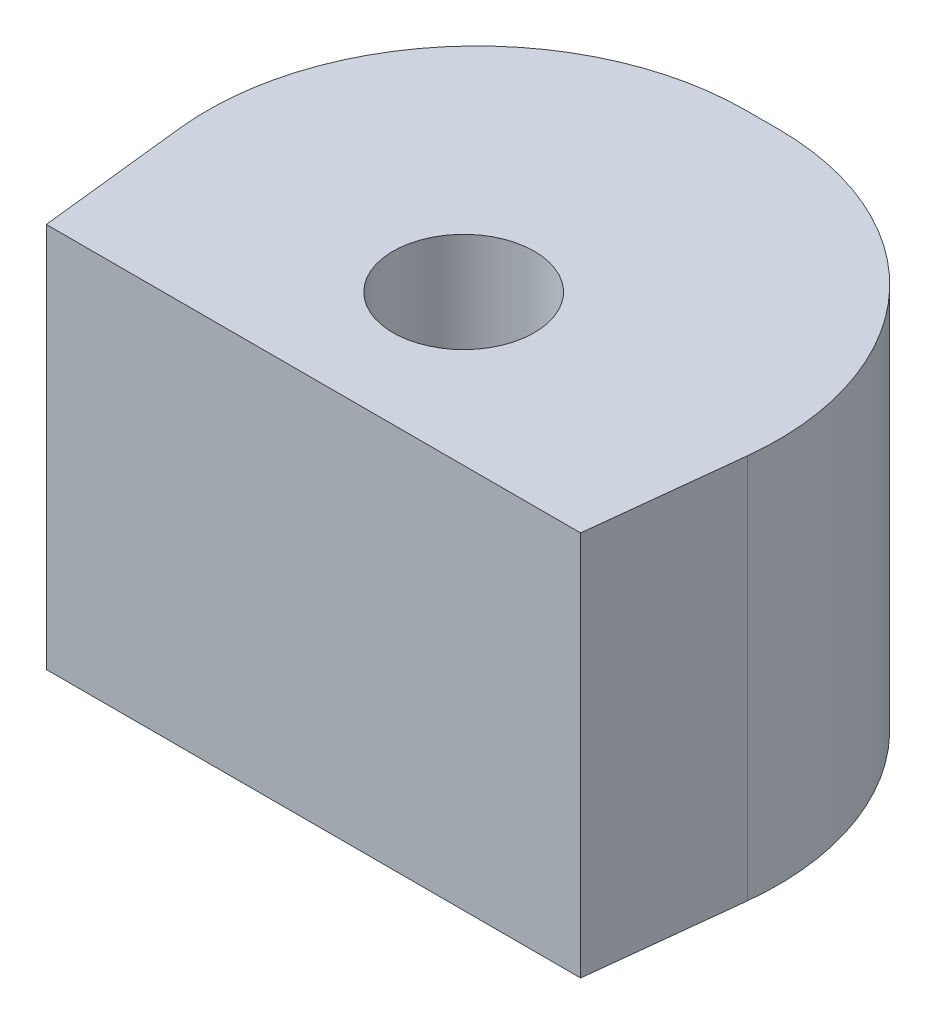
SolidWorks part; units mm, degrees
ref_plane "Front Plane" through (0, 0, 0) normal (0, 0, 1) x (1, 0, 0)
ref_plane "Top Plane" through (0, 0, 0) normal (0, 1, 0) x (1, 0, 0)
ref_plane "Right Plane" through (0, 0, 0) normal (1, 0, 0) x (0, 0, -1)
sketch "Sketch1" plane through (0, 0, 0) normal (0, 1, 0) x (1, 0, 0)
  line L0 (1.1081, 1.7265) -> (-45.0799, 1.7265) construction
  line L1 (-45.0799, 1.7265) -> (-45.0799, -11.2275) construction
  line L2 (-45.0799, -11.2275) -> (43.7517, -11.2275) construction
  line L3 (1.1081, 103.3269) -> (1.1081, -99.8738) construction
  line L4 (-45.0799, -11.2275) -> (-45.0799, -20.7525) construction
  line L5 (-28.2049, 1.7265) -> (-28.2049, -3.6075) construction
  line L6 (-9.9553, -3.6075) -> (-6.7697, -3.6075)
  line L7 (-28.2049, -3.6075) -> (-9.9553, -3.6075) construction
  line L8 (-6.7697, -3.6075) -> (1.1081, -3.6075) construction
  line L9 (8.9859, -3.6075) -> (12.1715, -3.6075)
  line L10 (12.1715, -3.6075) -> (18.1346, -3.6075) construction
  line L11 (12.1715, -3.6075) -> (18.1346, -3.6075) construction
  line L12 (18.1346, -3.6075) -> (29.3788, -3.6075) construction
  line L13 (1.1081, -3.6075) -> (8.9859, -3.6075) construction
  line L14 (-6.7697, -3.6075) -> (8.9859, -3.6075)
  circle A0 centre (1.1081, -11.3265) radius 1.9844 construction
  circle A1 centre (1.1081, -11.3265) radius 1.9844
  spline S0 degree 3 poles (1.1081, -99.8738) (4.5273, -73.5318) (7.9866, -47.1872) (10.6029, -20.7525) knots 0 0 0 0 0.38497 0.38497 0.38497 0.38497
  spline S3 degree 3 poles (1.1081, -99.8738) (-2.3112, -73.5318) (-5.7704, -47.1872) (-8.3867, -20.7525) knots 0 0 0 0 0.38497 0.38497 0.38497 0.38497
  spline S4 degree 3 poles (10.6029, -20.7525) (11.1, -15.7302) (11.6306, -10.016) (12.114, -4.2968) (12.1715, -3.6075) knots 0.38497 0.38497 0.38497 0.38497 0.458109 0.468132 0.468132 0.468132 0.468132
  spline S5 degree 3 poles (-8.3867, -20.7525) (-8.8838, -15.7302) (-9.4144, -10.016) (-9.8978, -4.2968) (-9.9553, -3.6075) knots 0.38497 0.38497 0.38497 0.38497 0.458109 0.468132 0.468132 0.468132 0.468132
  spline S8 degree 3 poles (12.1715, -3.6075) (12.8364, 4.367) (14.1908, 23.6726) (14.0058, 48.0803) (13.0188, 67.5796) (11.3266, 78.9472) (9.5869, 86.9693) (8.1237, 93.6397) (6.4505, 97.563) (4.8164, 101.3994) (2.3437, 102.5279) (1.1081, 103.3269) knots 0.468132 0.468132 0.468132 0.468132 0.584075 0.748482 0.821537 0.866809 0.914778 0.94069 0.965303 0.976863 1 1 1 1 construction
  spline S9 degree 3 poles (1.1081, 99.6196) (1.2739, 99.518) (1.6209, 99.2976) (2.0134, 99.0137) (2.3095, 98.7539) (2.4667, 98.5788) (2.6076, 98.3713) (2.8163, 97.9774) (3.0534, 97.4394) (3.4327, 96.5453) (3.8774, 95.496) (4.541, 93.8448) (5.2023, 91.9048) (5.8236, 89.3366) (6.4213, 86.5662) (7.0145, 83.8293) (7.767, 80.1951) (8.6007, 75.6781) (9.6391, 68.4081) (10.3034, 59.2354) (10.6788, 47.9926) (10.8555, 36.7918) (10.7415, 25.5951) (10.3009, 14.4244) (9.6564, 4.6878) (9.1767, -1.3266) (8.9859, -3.6075) knots 0.118744 0.118744 0.118744 0.118744 0.122149 0.125554 0.12896 0.132365 0.13577 0.139175 0.142581 0.145986 0.152796 0.159607 0.173228 0.186849 0.20047 0.214091 0.227711 0.254953 0.282195 0.336679 0.391163 0.445646 0.50013 0.554614 0.609098 0.642376 0.642376 0.642376 0.642376 construction
  spline S10 degree 3 poles (-7.1984, 1.7265) (-7.237, 2.2289) (-7.5577, 6.4638) (-8.0847, 14.4244) (-8.5253, 25.5951) (-8.6393, 36.7918) (-8.4626, 47.9926) (-8.0872, 59.2354) (-7.4229, 68.4081) (-6.3845, 75.6781) (-5.5508, 80.1951) (-4.7983, 83.8293) (-4.2051, 86.5662) (-3.6074, 89.3366) (-2.9861, 91.9048) (-2.3248, 93.8448) (-1.6612, 95.496) (-1.2165, 96.5453) (-0.8372, 97.4394) (-0.6001, 97.9774) (-0.3914, 98.3713) (-0.2505, 98.5788) (-0.0933, 98.7539) (0.2028, 99.0137) (0.5953, 99.2976) (0.9423, 99.518) (1.1081, 99.6196) knots 0.492798 0.492798 0.492798 0.492798 0.50013 0.554614 0.609098 0.663581 0.718065 0.772549 0.827033 0.854275 0.881516 0.895137 0.908758 0.922379 0.936 0.949621 0.956432 0.963242 0.966647 0.970053 0.973458 0.976863 0.980268 0.983674 0.987079 0.990484 0.990484 0.990484 0.990484 construction
  spline S11 degree 3 poles (-10.3826, 1.7265) (-10.8572, 7.9268) (-11.9611, 25.4575) (-11.7896, 48.0803) (-10.8026, 67.5796) (-9.1104, 78.9472) (-7.3707, 86.9693) (-5.9075, 93.6397) (-4.2343, 97.563) (-2.6002, 101.3994) (-0.1276, 102.5279) (1.1081, 103.3269) knots 0.493976 0.493976 0.493976 0.493976 0.584075 0.748482 0.821537 0.866809 0.914778 0.94069 0.965303 0.976863 1 1 1 1 construction
  spline S12 degree 3 poles (-9.9553, -3.6075) (-10.1035, -1.8299) (-10.2465, -0.0519) (-10.3826, 1.7265) knots 0.468132 0.468132 0.468132 0.468132 0.493976 0.493976 0.493976 0.493976 construction
  spline S13 degree 3 poles (-6.7697, -3.6075) (-6.9185, -1.8292) (-7.0618, -0.0511) (-7.1984, 1.7265) knots 0.466852 0.466852 0.466852 0.466852 0.492798 0.492798 0.492798 0.492798 construction
  dimension "D4" = 3.9688
  dimension "D1" = 12.954
  dimension "D2" = 9.525
  dimension "D3" = 5.334
extrude "Boss-Extrude1" add sketch "Sketch1" along normal blind 169.8727
sketch "Sketch2" plane through (0, 169.8727, 0) normal (0, 1, 0) x (1, 0, 0)
  line L1 (-9.9553, -3.6075) -> (25.8085, -3.6075)
  line L2 (-9.9553, -3.6075) -> (-9.9553, -26.3125)
  line L3 (-9.9553, -26.3125) -> (25.8085, -26.3125)
  line L4 (25.8085, -3.6075) -> (25.8085, -26.3125)
  circle A0 centre (1.1081, -11.3265) radius 1.9844 construction
  dimension "D1" = 14.986
extrude "Cut-Extrude1" cut sketch "Sketch2" against normal blind 23.0581
extrude "Cut-Extrude2" cut sketch "Sketch2<2>" along normal blind 23.0581 from surface starting at face at (-1.1046, 0, 29.7187)
sketch "Sketch2<2>" plane through (0, 169.8727, 0) normal (0, 1, 0) x (1, 0, 0) same geometry as "Sketch2"
fillet "Fillet1" radius 7.62 6 edges at (-7.8242, 11.5291, 26.3125) (10.0403, 11.5291, 26.3125) (12.1715, 84.9363, 3.6075) (-7.8242, 158.3436, 26.3125) (10.0403, 158.3436, 26.3125)
sketch "Sketch6" plane through (0, 0, 0) normal (0, -1, 0) x (1, 0, 0)
  line L0 (1.1081, 3.6075) -> (1.1081, 99.8738) construction
  line L1 (-1.6395, 3.6075) -> (3.8557, 3.6075) construction
  line L2 (-6.9254, 34.7606) -> (9.1416, 34.7606) construction
  circle A0 centre (1.1081, 71.9338) radius 2
  circle A1 centre (1.1081, 34.7606) radius 2
  dimension "D1" = 4
  dimension "D2" = 27.94
extrude "Cut-Extrude3" cut sketch "Sketch6" against normal through all both and the other way through all
sketch "Sketch7" plane through (0, 0, 0) normal (1, 0, 0) x (0, 0, -1)
  line L0 (-3.6075, 146.8145) -> (-3.6075, 23.0581) construction
  line L1 (-99.8738, 0) -> (-3.6075, 0)
  line L2 (-99.8738, 0) -> (-99.8738, 154.1951)
  line L3 (-99.8738, 154.1951) -> (-3.6075, 154.1951)
  line L4 (-3.6075, 0) -> (-3.6075, 154.1951)
  line L6 (-99.8738, 169.8727) -> (-3.6075, 169.8727)
  line L7 (-99.8738, 169.8727) -> (-99.8738, 165.1069)
  line L8 (-99.8738, 165.1069) -> (-3.6075, 165.1069)
  line L9 (-3.6075, 169.8727) -> (-3.6075, 165.1069)
  dimension "D2" = 10.9118
extrude "Cut-Extrude4" cut sketch "Sketch7" against normal through all both and the other way through all
sketch "Sketch8" plane through (0, 154.1951, 0) normal (0, -1, 0) x (1, 0, 0)
  line L1 (-35.7382, 103.9976) -> (19.5961, 103.9976)
  line L2 (-35.7382, 103.9976) -> (-35.7382, 39.0125)
  line L3 (-35.7382, 39.0125) -> (19.5961, 39.0125)
  line L4 (19.5961, 103.9976) -> (19.5961, 39.0125)
  dimension "D1" = 12.7
extrude "Cut-Extrude5" cut sketch "Sketch8" against normal through all both
